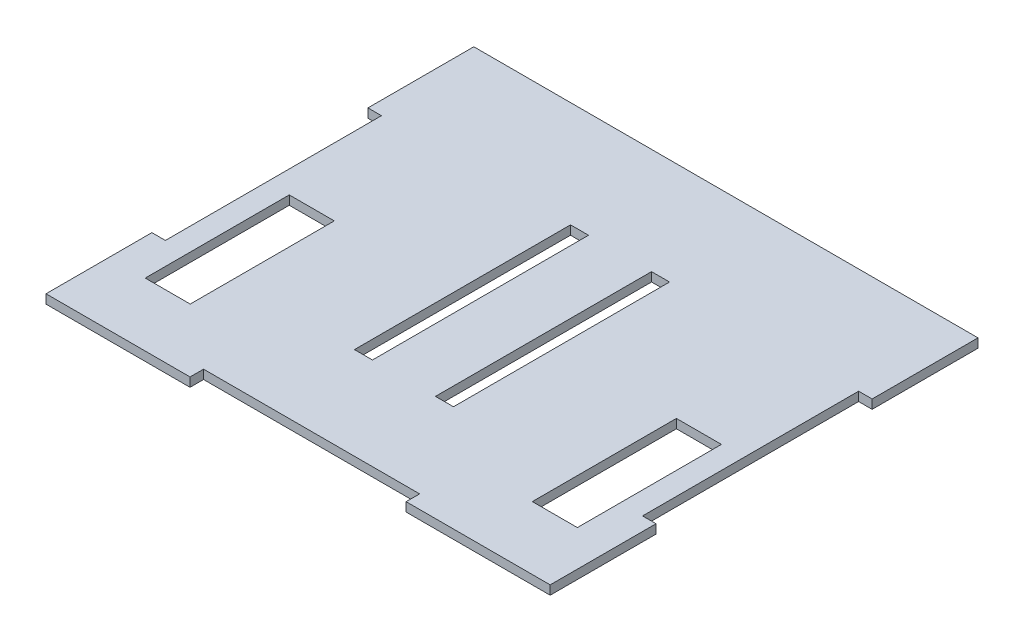
SolidWorks part; units mm, degrees
ref_plane "Front Plane" through (0, 0, 0) normal (0, 0, 1) x (1, 0, 0)
ref_plane "Top Plane" through (0, 0, 0) normal (0, 1, 0) x (1, 0, 0)
ref_plane "Right Plane" through (0, 0, 0) normal (1, 0, 0) x (0, 0, -1)
sketch "Sketch1" plane through (0, 0, 0) normal (0, 1, 0) x (1, 0, 0)
  line L1 (-177.8, -177.8) -> (-76.2, -177.8)
  line L2 (-177.8, -177.8) -> (-177.8, -103.124)
  line L4 (177.8, -177.8) -> (177.8, -103.124)
  line L5 (177.8, 123.952) -> (-177.8, 123.952)
  line L9 (-177.8, 49.276) -> (-168.275, 49.276)
  line L10 (177.8, 49.276) -> (168.275, 49.276)
  line L12 (177.8, -103.124) -> (168.275, -103.124)
  line L13 (168.275, 49.276) -> (168.275, -103.124)
  line L14 (-168.275, 49.276) -> (-168.275, -103.124)
  line L15 (-177.8, -103.124) -> (-168.275, -103.124)
  line L16 (177.8, 49.276) -> (177.8, 123.952)
  line L17 (-177.8, 49.276) -> (-177.8, 123.952)
  line L18 (76.2, -177.8) -> (177.8, -177.8)
  line L20 (76.2, -177.8) -> (76.2, -168.275)
  line L21 (76.2, -168.275) -> (-76.2, -168.275)
  line L22 (-76.2, -177.8) -> (-76.2, -168.275)
  point P0 (0, 0)
  point P16 (168.275, -26.924)
  point P25 (0, -168.275)
  dimension "D3" = 301.752
  dimension "D1" = 152.4
  dimension "D5" = 9.525
  dimension "D6" = 355.6
  dimension "D2" = 150.876
  dimension "D8" = 152.4
  dimension "D9" = 177.8
  dimension "D10" = 9.525
extrude "Boss-Extrude1" add sketch "Sketch1" along normal blind 6.35
sketch "Sketch4" plane through (0, 6.35, 0) normal (0, 1, 0) x (1, 0, 0)
  line L0 (152.4, -133.223) -> (152.4, -31.623)
  line L1 (152.4, -31.623) -> (120.65, -31.623)
  line L2 (120.65, -31.623) -> (120.65, -133.223)
  line L3 (120.65, -133.223) -> (152.4, -133.223)
  line L4 (0, -168.275) -> (0, 123.952) construction
  line L5 (-76.2, -168.275) -> (76.2, -168.275) construction
  line L11 (177.8, 123.952) -> (-177.8, 123.952) construction
  line L16 (-120.65, -31.623) -> (-120.65, -133.223)
  line L17 (-152.4, -31.623) -> (-120.65, -31.623)
  line L18 (-152.4, -133.223) -> (-152.4, -31.623)
  line L19 (-120.65, -133.223) -> (-152.4, -133.223)
  line L20 (76.2, -177.8) -> (177.8, -177.8) construction
  dimension "D1" = 101.6
  dimension "D2" = 120.65
  dimension "D4" = 44.577
  dimension "1" = 31.75
sketch "Sketch13" plane through (0, 6.35, 0) normal (0, 1, 0) x (1, 0, 0)
  line L0 (-177.8, 49.276) -> (177.8, 49.276) construction
  line L2 (-177.8, -103.124) -> (177.8, -103.124) construction
  line L3 (-34.925, 49.276) -> (-34.925, -103.124)
  line L4 (0, 49.276) -> (0, -103.124) construction
  line L5 (-34.925, 49.276) -> (-22.225, 49.276)
  line L6 (-22.225, 49.276) -> (-22.225, -103.124)
  line L7 (-22.225, -103.124) -> (-34.925, -103.124)
  line L8 (22.225, 49.276) -> (22.225, -103.124)
  line L9 (34.925, 49.276) -> (22.225, 49.276)
  line L10 (34.925, 49.276) -> (34.925, -103.124)
  line L11 (22.225, -103.124) -> (34.925, -103.124)
  dimension "D1" = 12.7
  dimension "D2" = 22.225
extrude "Cut-Extrude8" cut sketch "Sketch13" against normal through all
extrude "Cut-Extrude9" cut sketch "Sketch4" against normal through all and the other way blind 2.54
sketch "Bend-Lines1" [suppressed] plane through (0, 0, 0) normal (0, 1, 0) x (1, 0, 0)
sketch "Bounding-Box1" [suppressed] plane through (0, 0, 0) normal (0, 1, 0) x (1, 0, 0)
equation "\"D2@Sketch1\"=\"D3@Sketch1\"/2"
equation "\"D9@Sketch1\"=\"D6@Sketch1\"/2"
